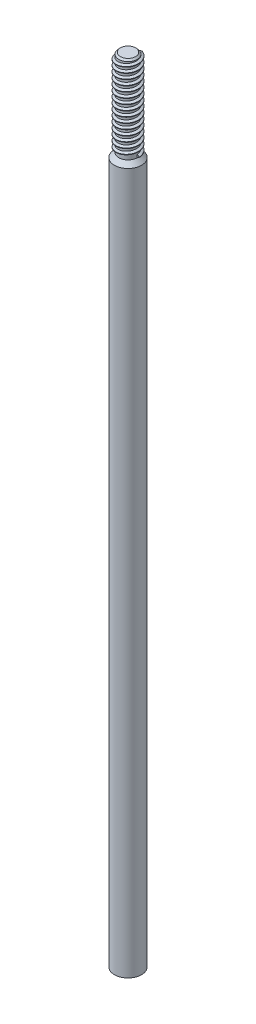
SolidWorks part; units mm, degrees
ref_plane "前视基准面" through (0, 0, 0) normal (0, 0, 1) x (1, 0, 0)
ref_plane "上视基准面" through (0, 0, 0) normal (0, 1, 0) x (1, 0, 0)
ref_plane "右视基准面" through (0, 0, 0) normal (1, 0, 0) x (0, 0, -1)
sketch "草图1" plane through (0, 0, 0) normal (0, 1, 0) x (1, 0, 0)
  circle A0 centre (0, 0) radius 2.5
  dimension "D1" = 5
extrude "凸台-拉伸1" add sketch "草图1" along normal blind 130
chamfer "倒角1" distance 0.8 angle 45 1 edges at (0, 130, 2.5)
sketch "草图4" plane through (0, 130, 0) normal (0, 1, 0) x (1, 0, 0)
  circle A1 centre (0, 0) radius 1.7
  circle A2 centre (0, 0) radius 1.7
  dimension "D1" = 0
extrude "凸台-拉伸2" add sketch "草图4" along normal blind 16
thread "螺纹线1" pitch 0.7056 method extrude profile "螺纹线轮廓2" start angle 0, offset 0, length 15.2, pitch 1, diameter 3.4
ref_plane "基准面2" through (1.7, 130, 0) normal (0, 0, 1) x (1, 0, 0)
sketch "螺纹线轮廓2" plane through (1.7, 130, 0) normal (0, 0, 1) x (1, 0, 0)
  line L0 (0, 0) -> (0, 0.7056) construction
  line L1 (0, 0) -> (0.3819, 0.2205)
  line L2 (0.3819, 0.2205) -> (0.3819, 0.3087)
  line L3 (0.3819, 0.3087) -> (0, 0.5292)
  line L4 (0.3819, 0.2646) -> (0, 0.2646) construction
  line L11 (0, 0) -> (0, 0.5292)
  point P2 (0, 0)
  dimension "Pitch" = 0.7056
  dimension "Profile_Angle" = 60
  dimension "Profile_Land" = 0.0882
  dimension "Profile_Height" = 0.3819
chamfer "倒角7" distance 0.3 angle 45 1 edges at (0, 146, 1.7)
